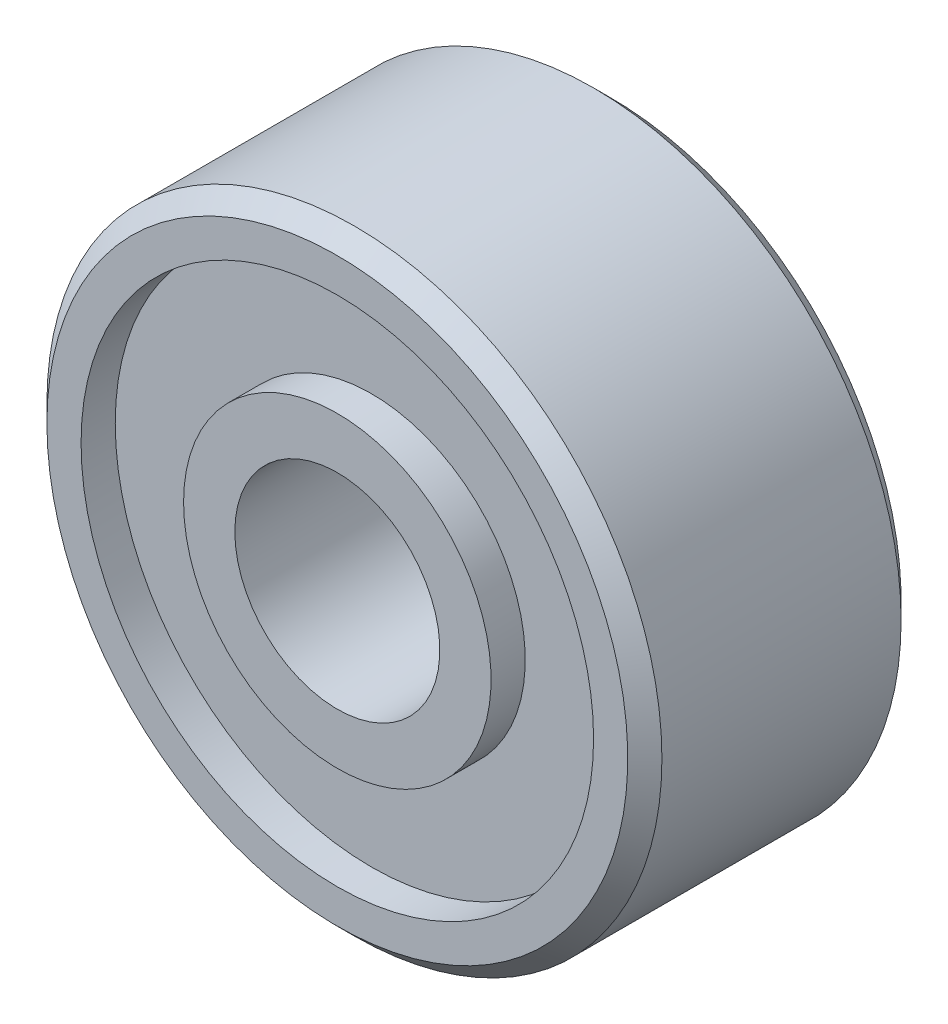
SolidWorks part; units mm, degrees
ref_plane "Front Plane" through (0, 0, 0) normal (0, 0, 1) x (1, 0, 0)
ref_plane "Top Plane" through (0, 0, 0) normal (0, 1, 0) x (1, 0, 0)
ref_plane "Right Plane" through (0, 0, 0) normal (1, 0, 0) x (0, 0, -1)
ref_plane "Plane1" through (0, 0, 0) normal (0, -1, 0) x (1, 0, 0)
sketch "Sketch1" plane through (0, 0, 0) normal (0, -1, 0) x (1, 0, 0)
  line L0 (4.5, 1.25) -> (4.25, 1.5)
  line L1 (4.25, 1.5) -> (3.75, 1.5)
  line L2 (3.75, 1.5) -> (3.75, 1)
  line L3 (3.75, 1) -> (2.25, 1)
  line L4 (2.25, 1) -> (2.25, 1.5)
  line L5 (2.25, 1.5) -> (1.5, 1.5)
  line L6 (1.5, 1.5) -> (1.5, -2.5)
  line L7 (1.5, -2.5) -> (2.25, -2.5)
  line L8 (2.25, -2.5) -> (2.25, -2)
  line L9 (2.25, -2) -> (3.75, -2)
  line L10 (3.75, -2) -> (3.75, -2.5)
  line L11 (3.75, -2.5) -> (4.25, -2.5)
  line L12 (4.25, -2.5) -> (4.5, -2.25)
  line L13 (4.5, -2.25) -> (4.5, 1.25)
  line L14 (0, 2.5) -> (0, -2.5) construction
  dimension "D1" = 3
  dimension "D2" = 0.25
  dimension "D3" = 4.5
  dimension "D4" = 4
  dimension "D5" = 9
  dimension "D7" = 0.5
  dimension "D8" = 45
  dimension "D9" = 7.5
revolve "Revolve1" add sketch "Sketch1" angle 360 about L14 reverse direction yes
